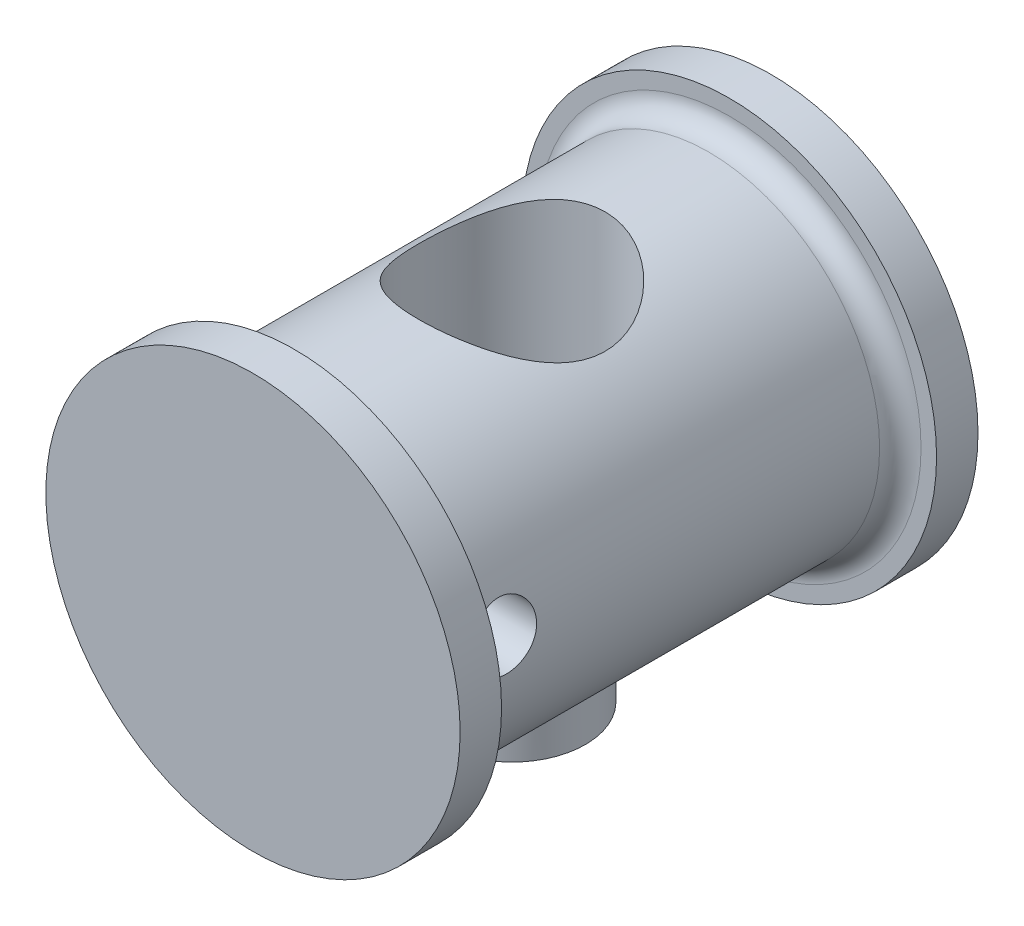
SolidWorks part; units mm, degrees
ref_plane "Ebene vorne" through (0, 0, 0) normal (0, 0, 1) x (1, 0, 0)
ref_plane "Ebene oben" through (0, 0, 0) normal (0, 1, 0) x (1, 0, 0)
ref_plane "Ebene rechts" through (0, 0, 0) normal (1, 0, 0) x (0, 0, -1)
sketch "Skizze1" plane through (0, 0, 0) normal (0, 0, 1) x (1, 0, 0)
  circle A0 centre (0, 0) radius 10
  dimension "D1" = 20
extrude "Aufsatz-Linear austragen1" add sketch "Skizze1" along normal blind 2
sketch "Skizze2" plane through (0, 0, 2) normal (0, 0, 1) x (1, 0, 0)
  circle A0 centre (0, 0) radius 8.25
  dimension "D1" = 16.5
extrude "Aufsatz-Linear austragen2" add sketch "Skizze2" along normal blind 21
sketch "Skizze3" plane through (0, 0, 23) normal (0, 0, 1) x (1, 0, 0)
  circle A0 centre (0, 0) radius 10
extrude "Aufsatz-Linear austragen3" add sketch "Skizze3" along normal blind 2
fillet "Verrundung1" radius 1 2 edges at (8.25, 0, 23) (8.25, 0, 2)
ref_plane "Ebene1" through (0, 0, 0) normal (0, 1, 0) x (1, 0, 0)
ref_plane "Ebene2" through (0, 0, 0) normal (-1, 0, 0) x (0, 0, 1)
sketch "Skizze4" plane through (0, 0, 0) normal (-1, 0, 0) x (0, 0, 1)
  line L0 (20.7012, 0) -> (-20.7012, 0) construction
  line L1 (23, 9.25) -> (23, -9.25) construction
  circle A0 centre (21, 1.05) radius 1.5
  dimension "D1" = 3
  dimension "D3" = 2
  dimension "D2" = 1.05
extrude "Schnitt-Linear austragen1" cut sketch "Skizze4" against normal blind 14 and the other way blind 14
sketch "Skizze5" plane through (0, 0, 0) normal (0, 1, 0) x (1, 0, 0)
  line L0 (0, 18.673) -> (0, -18.673) construction
  line L1 (10, 0) -> (-10, 0) construction
  circle A1 centre (0, -12.5) radius 4.5
  dimension "D1" = 9
  dimension "D2" = 12.5
extrude "Schnitt-Linear austragen2" cut sketch "Skizze5" along normal blind 14 and the other way blind 1
sketch "Skizze6" plane through (0, -1, 0) normal (0, 1, 0) x (1, 0, 0)
  line L0 (0, 18.673) -> (0, -18.673) construction
  line L1 (-10, -25) -> (10, -25) construction
  circle A0 centre (0, -12.5) radius 2.55
  dimension "D1" = 12.5
  dimension "D2" = 5.1
extrude "Schnitt-Linear austragen3" cut sketch "Skizze6" against normal blind 14
sketch "Skizze7" plane through (0, 0, 0) normal (0, 1, 0) x (1, 0, 0)
  circle A0 centre (0, -12.5) radius 2.55
  circle A1 centre (0, -12.5) radius 3.55
  dimension "D1" = 1
extrude "Aufsatz-Linear austragen4" add sketch "Skizze7" against normal blind 10
ref_plane "Ebene3" through (0, -10, 0) normal (0, -1, 0) x (-1, 0, 0)
